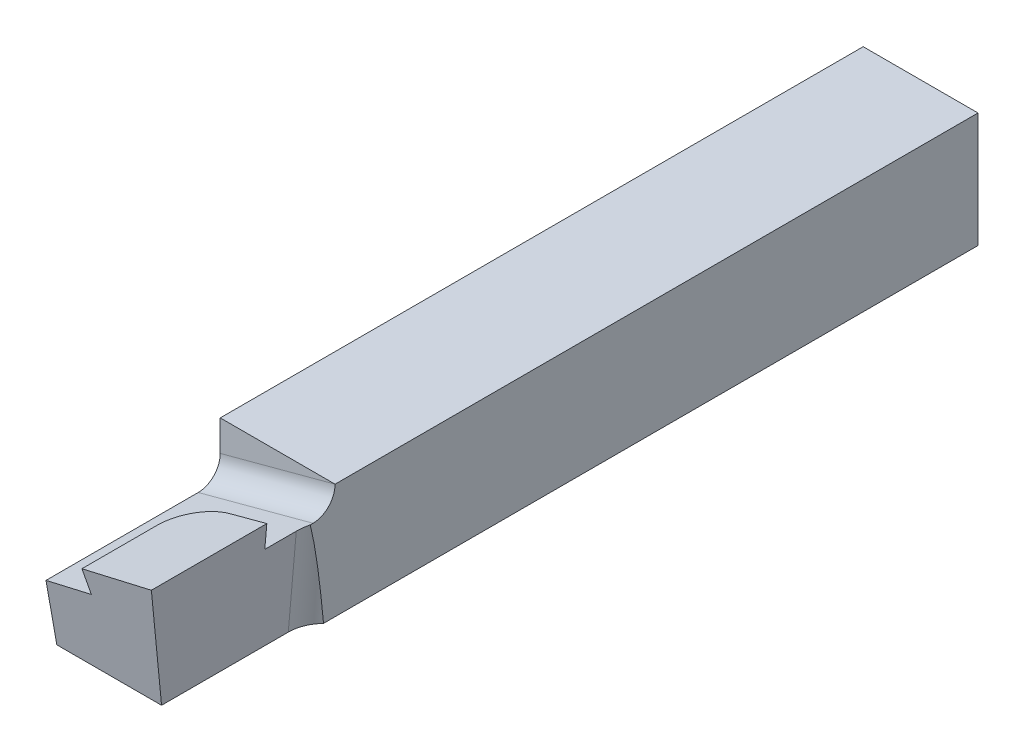
SolidWorks part; units mm, degrees
ref_plane "Front Plane" through (0, 0, 0) normal (0, 0, 1) x (1, 0, 0)
ref_plane "Top Plane" through (0, 0, 0) normal (0, 1, 0) x (1, 0, 0)
ref_plane "Right Plane" through (0, 0, 0) normal (1, 0, 0) x (0, 0, -1)
sketch "Sketch1" plane through (0, 0, 0) normal (0, 0, 1) x (1, 0, 0)
  line L1 (-3.9688, -3.9688) -> (3.9688, -3.9688)
  line L2 (-3.9688, -3.9688) -> (-3.9688, 3.9688)
  line L3 (-3.9688, 3.9688) -> (3.9688, 3.9688)
  line L4 (3.9688, -3.9688) -> (3.9688, 3.9688)
  line L5 (-3.9688, -3.9688) -> (3.9688, 3.9688) construction
  line L6 (-3.9688, 3.9688) -> (3.9688, -3.9688) construction
  point P0 (0, 0)
  dimension "D1" = 7.9375
extrude "Boss-Extrude1" add sketch "Sketch1" along normal blind 57.15
sketch "Sketch2" plane through (0, 0, 57.15) normal (0, 0, 1) x (1, 0, 0)
  line L0 (-3.9688, 1.8419) -> (3.9688, 3.9688)
  line L1 (-3.9688, 3.9688) -> (-3.9688, -3.9688) construction
  line L2 (3.9688, 3.9688) -> (3.2743, -3.9688)
  line L3 (-3.9688, -3.9688) -> (3.9688, -3.9688) construction
  line L4 (3.2743, -3.9688) -> (-3.9688, -3.9688)
  line L5 (-3.9688, -3.9688) -> (-3.9688, 1.8419)
  line L6 (3.9688, 3.9688) -> (-3.9688, 3.9688) construction
  line L7 (3.9688, -3.9688) -> (3.9688, 3.9688) construction
  dimension "D1" = 15
  dimension "D2" = 5
extrude "Cut-Extrude1" cut sketch "Sketch2" against normal blind 12.7 flip side to cut
fillet "Fillet1" [suppressed] radius 2.54
fillet "Fillet2" radius 2.54 1 edges at (3.6215, 0, 44.45)
sketch "Sketch3" plane through (3.9688, 0, 0) normal (1, 0, 0) x (0, 0, -1)
  line L0 (-57.15, 3.9688) -> (-55.7504, -3.9688)
  line L1 (-46.99, -3.9688) -> (-57.15, -3.9688) construction
  line L2 (-55.7504, -3.9688) -> (-57.15, -3.9688)
  line L3 (-57.15, -3.9688) -> (-57.15, 3.9688)
  dimension "D1" = 10
extrude "Cut-Extrude2" cut sketch "Sketch3" against normal through all
sketch "Sketch4" plane through (-0.7263, 2.7107, 0) normal (-0.2588, 0.9659, 0) x (0.9659, 0.2588, 0)
  line L0 (4.8607, -57.15) -> (-3.3568, -56.775) construction
  line L1 (4.8607, -46.99) -> (4.8607, -57.15) construction
  line L2 (-5.9766, -44.45) -> (8.8954, -44.45)
  line L3 (4.8607, -57.15) -> (-0.3572, -56.9119)
  line L4 (4.8607, -57.15) -> (4.8607, -49.1667)
  line L5 (4.8607, -49.1667) -> (2.1828, -49.1667)
  line L6 (-0.3572, -56.9119) -> (-0.3572, -51.7067)
  line L7 (-5.9766, -44.45) -> (-5.9766, -56.9119)
  line L8 (-5.9766, -56.9119) -> (-0.3572, -56.9119)
  line L9 (4.8607, -57.15) -> (8.8954, -57.15)
  line L10 (8.8954, -57.15) -> (8.8954, -44.45)
  arc A0 (2.1828, -49.1667) -> (-0.3572, -51.7067) centre (2.1828, -51.7067) ccw
  line M1 (-3.3568, -56.775) -> (4.8607, -57.15)
  line M2 (4.8607, -57.15) -> (4.8607, -46.99)
  line M4 (-3.3568, -44.45) -> (-3.3568, -56.775)
  line M12 (4.8607, -46.99) -> (4.8607, -44.45)
  line M13 (4.8607, -44.45) -> (-3.3568, -44.45)
  dimension "D1" = 2.54
extrude "Cut-Extrude3" cut sketch "Sketch4" against normal blind 1.524 contours L7 L8 L2 M1 M4 | A0 L5 L6 M2 M12 M13 M4 M1 | L9 L10 L2 M12 M2
fillet "Fillet3" radius 1.524 1 edges at (0, 1.3276, 44.45)
